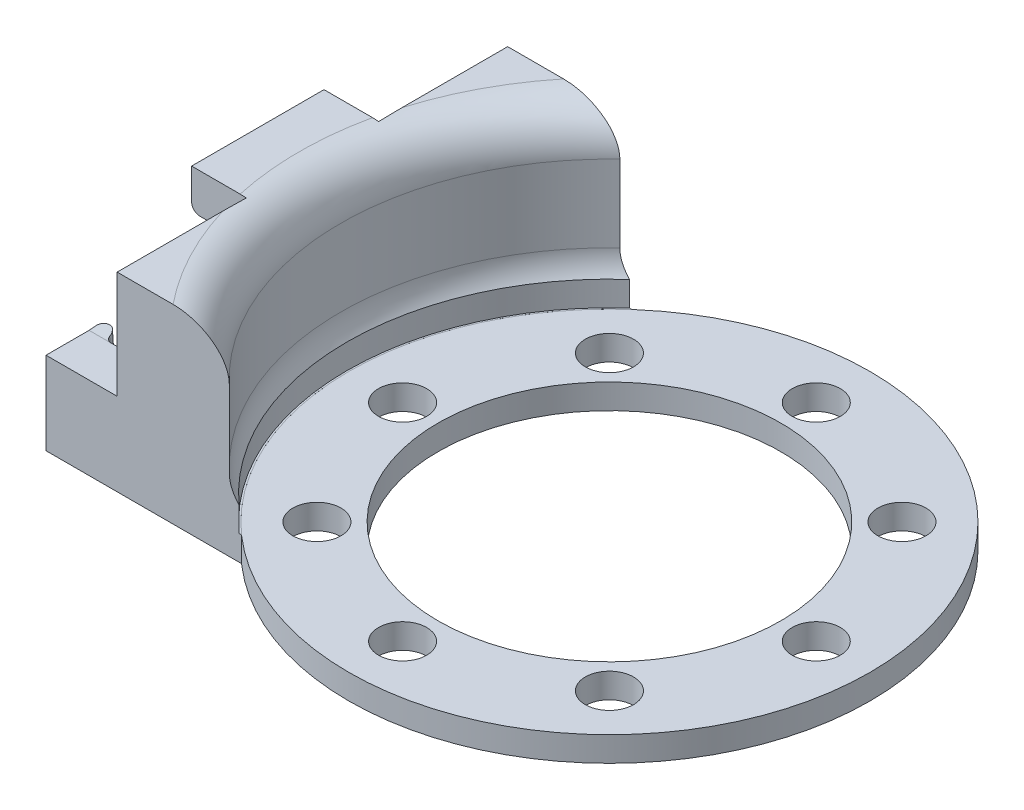
SolidWorks part; units mm, degrees
ref_plane "前视基准面" through (0, 0, 0) normal (0, 0, 1) x (1, 0, 0)
ref_plane "上视基准面" through (0, 0, 0) normal (0, 1, 0) x (1, 0, 0)
ref_plane "右视基准面" through (0, 0, 0) normal (1, 0, 0) x (0, 0, -1)
sketch "草图1" plane through (0, 0, 0) normal (0, 1, 0) x (1, 0, 0)
  circle A0 centre (0, 0) radius 31.5
  circle A1 centre (0, 0) radius 20.714
  circle A2 centre (0, -25) radius 2.9098
  circle A3 centre (0, 0) radius 25 construction
  circle A4 centre (-17.6777, -17.6777) radius 2.9098
  circle A5 centre (-25, 0) radius 2.9098
  circle A6 centre (-17.6777, 17.6777) radius 2.9098
  circle A7 centre (0, 25) radius 2.9098
  circle A8 centre (17.6777, 17.6777) radius 2.9098
  circle A9 centre (25, 0) radius 2.9098
  circle A10 centre (17.6777, -17.6777) radius 2.9098
  point P24 (0, 0)
  dimension "D1" = 8
  dimension "D2" = 50
  dimension "D3" = 63
extrude "凸台-拉伸1" add sketch "草图1" along normal blind 3
sketch "草图2" plane through (0, 0, 0) normal (0, 1, 0) x (1, 0, 0)
  line L0 (-55, 0) -> (55, 0) construction
  line L2 (-44.5, 23.6) -> (-44.5, -23.6)
  line L3 (0, -55) -> (0, 55) construction
  line L4 (-44.5, 23.6) -> (-20.8636, 23.6)
  line L5 (-44.5, -23.6) -> (-20.8636, -23.6)
  circle A1 centre (0, 0) radius 31.5 construction
  arc A2 (-20.8636, 23.6) -> (-20.8636, -23.6) centre (0, 0) ccw
  dimension "D1" = 23.6
  dimension "D2" = 23.6
  dimension "D3" = 44.5
extrude "凸台-拉伸2" add sketch "草图2" along normal blind 23 separate body
sketch "草图3" plane through (-44.5, 0, 0) normal (-1, 0, 0) x (0, 0, 1)
  line L1 (0, -55) -> (0, 55) construction
  line L6 (-8, 23) -> (-8, 18.2512)
  line L7 (8, 23) -> (8, 18.2512)
  line L8 (23.6, 0) -> (-18, 0) construction
  line L9 (-23.6, 23) -> (23.6, 23) construction
  line L10 (-23.6, 23) -> (23.6, 23)
  line L11 (-23.6, 23) -> (-23.6, 0) construction
  line L12 (-23.6, 23) -> (-23.6, 10)
  line L13 (-18.3928, 10) -> (-23.6, 10)
  line L14 (0, 23.068) -> (0, 5.0033) construction
  line L15 (18.3928, 10) -> (23.6, 10)
  line L17 (-23.6, 0) -> (23.6, 0)
  line L18 (23.6, 0) -> (23.6, 23)
  line L19 (23.6, 23) -> (-23.6, 23)
  line L20 (-23.6, 23) -> (-23.6, 0)
  line L21 (-18, 0) -> (23.6, 0)
  line L22 (23.6, 0) -> (23.6, 23)
  line L23 (23.6, 23) -> (-23.6, 23)
  line L24 (-23.6, 23) -> (-23.6, 10)
  arc A0 (-18, 0) -> (-18.3928, 10) centre (-145.5, 0) ccw
  arc A1 (-8, 18.2512) -> (8, 18.2512) centre (0, 145.5) ccw
  arc A2 (18, 0) -> (18.3928, 10) centre (145.5, 0) cw
  line M16 (-23.6, 0) -> (23.6, 0)
  line M17 (23.6, 0) -> (23.6, 23)
  line M18 (23.6, 23) -> (-23.6, 23)
  line M19 (-23.6, 23) -> (-23.6, 0)
  dimension "D1" = 8
  dimension "D4" = 8
  dimension "D6" = 0
  dimension "D7" = 10
extrude "切除-拉伸1" cut sketch "草图3" against normal blind 8.6 contours A2 L15 L7 A1 L6 L13 A0 M16 M17 M18 M19
sketch "草图5" plane through (0, 23, 0) normal (0, 1, 0) x (1, 0, 0)
  circle A0 centre (0, 0) radius 32.5
  dimension "D1" = 65
extrude "切除-拉伸2" cut sketch "草图5" against normal blind 17
fillet "圆角1" radius 5 1 edges at (-32.5, 23, 0)
fillet "圆角2" radius 1.8 3 edges at (-35.9, 5.0039, 18.0982) (-35.9, 18, 0) (-35.9, 5.0039, -18.0982)
sketch "草图6" plane through (0, 0, 0) normal (0, 1, 0) x (1, 0, 0)
  line L0 (-44.5, -18) -> (-44.5, -16)
  line L1 (-44.5, -18) -> (-42.5, -18)
  line L2 (-18.8311, 0) -> (-38.0928, 0) construction
  line L3 (-55, 0) -> (55, 0) construction
  arc A0 (-42.5, -18) -> (-44.5, -16) centre (-44.5, -18) ccw
sweep "扫描1" add profiles "草图6" path edge at (-44.5, 5.0039, 18.0982)
sketch "草图7" plane through (0, 0, 0) normal (0, 1, 0) x (1, 0, 0)
  line L0 (-44.5, 18) -> (-44.5, 16)
  line L1 (-42.5, 18) -> (-44.5, 18)
  arc A0 (-44.5, 16) -> (-42.5, 18) centre (-44.5, 18) ccw
sweep "扫描2" add profiles "草图7" path edge at (-44.5, 5.0039, -18.0982)
fillet "圆角4" radius 0.8 3 edges at (-44.5, 5.0823, 16.0998) (-44.5, 5.0823, -16.0998)
fillet "圆角5" radius 0.8 1 edges
sketch "草图8" plane through (-44.5, 0, 0) normal (-1, 0, 0) x (0, 0, 1)
  line L1 (-27.7116, 35.6073) -> (11.0815, 35.6073)
  line L2 (-27.7116, 35.6073) -> (-27.7116, 15.6335)
  line L3 (-27.7116, 15.6335) -> (11.0815, 15.6335)
  line L4 (11.0815, 35.6073) -> (11.0815, 15.6335)
  line L5 (-27.7116, 35.6073) -> (11.0815, 15.6335) construction
  line L6 (-27.7116, 15.6335) -> (11.0815, 35.6073) construction
  point P0 (-8.315, 25.6204)
extrude "切除-拉伸3" cut sketch "草图8" against normal blind 2
fillet "圆角6" radius 1 1 edges at (-42.5, 18, 0)
sketch "草图9" plane through (0, 6, 0) normal (0, 1, 0) x (1, 0, 0)
  circle A0 centre (0, 0) radius 31.7
  circle A1 centre (0, 0) radius 31.5 construction
  dimension "D1" = 0.2
extrude "切除-拉伸4" cut sketch "草图9" against normal blind 3
fillet "圆角7" radius 5 1 edges at (-32.5, 6, 0)
